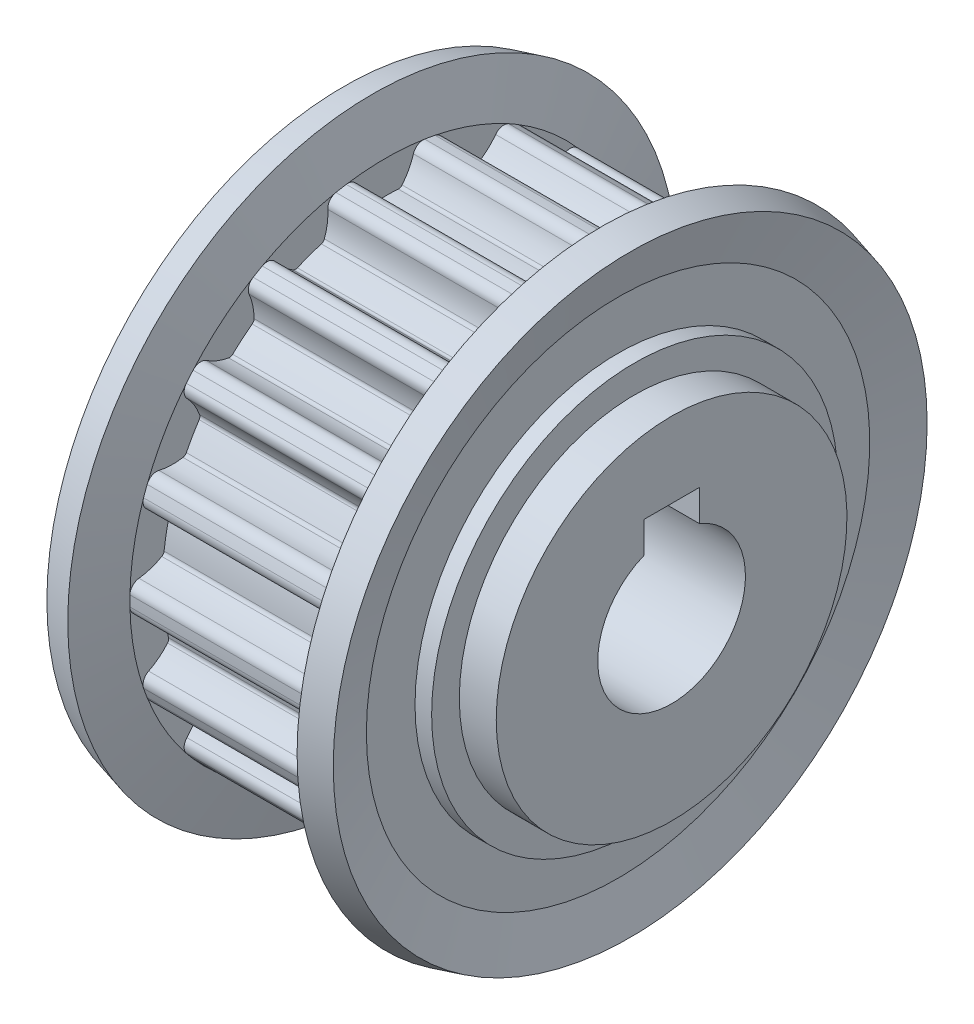
SolidWorks part; units mm, degrees
material "AISI 1045 강, 냉간압연"
ref_plane "정면" through (0, 0, 0) normal (0, 0, 1) x (1, 0, 0)
ref_plane "윗면" through (0, 0, 0) normal (0, 1, 0) x (1, 0, 0)
ref_plane "우측면" through (0, 0, 0) normal (1, 0, 0) x (0, 0, -1)
ref_plane "평면1" through (0, 0, 0) normal (0, 0, 1) x (1, 0, 0)
sketch "스케치1" plane through (0, 0, 0) normal (0, 0, 1) x (1, 0, 0)
  line L0 (0, 0) -> (0, 11)
  line L1 (0, 11) -> (0.9, 11)
  line L2 (0.9, 11) -> (0.9, 13.6344)
  line L3 (0.9, 13.6344) -> (0.2431, 16.0859)
  line L4 (0.2431, 16.0859) -> (1.7886, 16.5)
  line L5 (1.7886, 16.5) -> (2.5, 13.845)
  line L6 (2.5, 13.845) -> (13.5, 13.845)
  line L7 (13.5, 13.845) -> (14.2114, 16.5)
  line L8 (14.2114, 16.5) -> (15.7569, 16.0859)
  line L9 (15.7569, 16.0859) -> (15.1, 13.6344)
  line L10 (15.1, 13.6344) -> (15.1, 11)
  line L11 (15.1, 11) -> (16, 11)
  line L12 (16, 11) -> (16, 9.5)
  line L13 (16, 9.5) -> (25, 9.5)
  line L14 (25, 9.5) -> (25, 0)
  line L15 (25, 0) -> (0, 0)
  line L16 (25, 0) -> (0, 0) construction
revolve "회전1" add sketch "스케치1" angle 360 about L16 reverse direction yes
ref_plane "평면2" through (0, 0, 0) normal (0, 0, 1) x (1, 0, 0)
sketch "스케치2" plane through (0, 0, 0) normal (0, 0, 1) x (1, 0, 0)
  line L0 (0, 0) -> (0, 4)
  line L1 (0, 4) -> (25, 4)
  line L2 (25, 4) -> (25, 0)
  line L3 (25, 0) -> (0, 0)
  line L4 (25, 0) -> (0, 0) construction
revolve "컷-회전1" cut sketch "스케치2" angle 360 about L4 reverse direction yes
ref_plane "평면3" through (2.5, 0, 0) normal (1, 0, 0) x (0, 0, -1)
sketch "스케치3" plane through (2.5, 0, 0) normal (1, 0, 0) x (0, 0, -1)
  line L0 (2.1243, 13.6811) -> (2.1243, 14.1666)
  line L1 (-2.1243, 14.1666) -> (-2.1243, 13.6811)
  arc A0 (-2.1243, 13.6811) -> (-1.5129, 13.295) centre (-2.0399, 13.1376) cw
  arc A1 (-1.5129, 13.295) -> (-0.8988, 12.1454) centre (1.625, 14.2325) ccw
  arc A2 (-0.8988, 12.1454) -> (-0.6918, 12.0552) centre (-0.7062, 12.3048) ccw
  arc A3 (-0.6918, 12.0552) -> (0.6918, 12.0552) centre (0, 0) cw
  arc A4 (0.6918, 12.0552) -> (0.8988, 12.1454) centre (0.7062, 12.3048) ccw
  arc A5 (0.8988, 12.1454) -> (1.5129, 13.295) centre (-1.625, 14.2325) ccw
  arc A6 (1.5129, 13.295) -> (2.1243, 13.6811) centre (2.0399, 13.1376) cw
  arc A7 (2.1243, 14.1666) -> (-2.1243, 14.1666) centre (0, 0) ccw
extrude "컷-돌출1" cut sketch "스케치3" along normal blind 11
ref_plane "평면4" through (2.5, 0, 0) normal (1, 0, 0) x (0, 0, -1)
sketch "스케치4" plane through (2.5, 0, 0) normal (1, 0, 0) x (0, 0, -1)
  line L0 (6.6754, 12.1294) -> (6.8415, 12.5857)
  line L1 (2.8491, 14.0388) -> (2.683, 13.5825)
  arc A0 (2.683, 13.5825) -> (3.1255, 13.0107) centre (2.5764, 13.043) cw
  arc A1 (3.1255, 13.0107) -> (3.3094, 11.7204) centre (6.3948, 12.8184) ccw
  arc A2 (3.3094, 11.7204) -> (3.473, 11.5648) centre (3.5449, 11.8042) ccw
  arc A3 (3.473, 11.5648) -> (4.7732, 11.0915) centre (0, 0) cw
  arc A4 (4.7732, 11.0915) -> (4.9986, 11.1056) centre (4.872, 11.3212) ccw
  arc A5 (4.9986, 11.1056) -> (5.9689, 11.9758) centre (3.3408, 13.93) ccw
  arc A6 (5.9689, 11.9758) -> (6.6754, 12.1294) centre (6.4102, 11.6476) cw
  arc A7 (6.8415, 12.5857) -> (2.8491, 14.0388) centre (0, 0) ccw
extrude "컷-돌출2" cut sketch "스케치4" along normal blind 11
ref_plane "평면5" through (2.5, 0, 0) normal (1, 0, 0) x (0, 0, -1)
sketch "스케치5" plane through (2.5, 0, 0) normal (1, 0, 0) x (0, 0, -1)
  line L0 (10.4213, 9.1148) -> (10.7334, 9.4868)
  line L1 (7.4788, 12.2177) -> (7.1667, 11.8458)
  arc A0 (7.1667, 11.8458) -> (7.3869, 11.1571) centre (6.882, 11.3752) cw
  arc A1 (7.3869, 11.1571) -> (7.1184, 9.8817) centre (10.3933, 9.8582) ccw
  arc A2 (7.1184, 9.8817) -> (7.2189, 9.6795) centre (7.3684, 9.8799) ccw
  arc A3 (7.2189, 9.6795) -> (8.2789, 8.7901) centre (0, 0) cw
  arc A4 (8.2789, 8.7901) -> (8.4955, 8.7262) centre (8.4503, 8.9721) ccw
  arc A5 (8.4955, 8.7262) -> (9.7049, 9.2121) centre (7.9037, 11.9473) ccw
  arc A6 (9.7049, 9.2121) -> (10.4213, 9.1148) centre (10.0073, 8.7527) cw
  arc A7 (10.7334, 9.4868) -> (7.4788, 12.2177) centre (0, 0) ccw
extrude "컷-돌출3" cut sketch "스케치5" along normal blind 11
ref_plane "평면6" through (2.5, 0, 0) normal (1, 0, 0) x (0, 0, -1)
sketch "스케치6" plane through (2.5, 0, 0) normal (1, 0, 0) x (0, 0, -1)
  line L0 (12.9103, 5.0008) -> (13.3308, 5.2436)
  line L1 (11.2065, 8.923) -> (10.786, 8.6802)
  arc A0 (10.786, 8.6802) -> (10.7573, 7.9578) centre (10.3575, 8.3354) cw
  arc A1 (10.7573, 7.9578) -> (10.0688, 6.8511) centre (13.1382, 5.709) ccw
  arc A2 (10.0688, 6.8511) -> (10.0942, 6.6267) centre (10.3032, 6.7639) ccw
  arc A3 (10.0942, 6.6267) -> (10.786, 5.4284) centre (0, 0) cw
  arc A4 (10.786, 5.4284) -> (10.9677, 5.2943) centre (11.0093, 5.5408) ccw
  arc A5 (10.9677, 5.2943) -> (12.2703, 5.3373) centre (11.5132, 8.5236) ccw
  arc A6 (12.2703, 5.3373) -> (12.9103, 5.0008) centre (12.3974, 4.8022) cw
  arc A7 (13.3308, 5.2436) -> (11.2065, 8.923) centre (0, 0) ccw
extrude "컷-돌출4" cut sketch "스케치6" along normal blind 11
ref_plane "평면7" through (2.5, 0, 0) normal (1, 0, 0) x (0, 0, -1)
sketch "스케치7" plane through (2.5, 0, 0) normal (1, 0, 0) x (0, 0, -1)
  line L0 (13.8421, 0.2836) -> (14.3203, 0.368)
  line L1 (13.5825, 4.552) -> (13.1043, 4.4677)
  arc A0 (13.1043, 4.4677) -> (12.8303, 3.7986) centre (12.5838, 4.2902) cw
  arc A1 (12.8303, 3.7986) -> (11.8048, 2.9942) centre (14.2985, 0.8711) ccw
  arc A2 (11.8048, 2.9942) -> (11.7519, 2.7747) centre (11.9952, 2.8321) ccw
  arc A3 (11.7519, 2.7747) -> (11.9922, 1.412) centre (0, 0) cw
  arc A4 (11.9922, 1.412) -> (12.117, 1.2239) centre (12.2404, 1.4413) ccw
  arc A5 (12.117, 1.2239) -> (13.3558, 0.8187) centre (13.7341, 4.0718) ccw
  arc A6 (13.3558, 0.8187) -> (13.8421, 0.2836) centre (13.2922, 0.2724) cw
  arc A7 (14.3203, 0.368) -> (13.5825, 4.552) centre (0, 0) ccw
extrude "컷-돌출5" cut sketch "스케치7" along normal blind 11
ref_plane "평면8" through (2.5, 0, 0) normal (1, 0, 0) x (0, 0, -1)
sketch "스케치8" plane through (2.5, 0, 0) normal (1, 0, 0) x (0, 0, -1)
  line L0 (13.1043, -4.4677) -> (13.5825, -4.552)
  line L1 (14.3203, -0.368) -> (13.8421, -0.2836)
  arc A0 (13.8421, -0.2836) -> (13.3558, -0.8187) centre (13.2922, -0.2724) cw
  arc A1 (13.3558, -0.8187) -> (12.117, -1.2239) centre (13.7341, -4.0718) ccw
  arc A2 (12.117, -1.2239) -> (11.9922, -1.412) centre (12.2404, -1.4413) ccw
  arc A3 (11.9922, -1.412) -> (11.7519, -2.7747) centre (0, 0) cw
  arc A4 (11.7519, -2.7747) -> (11.8048, -2.9942) centre (11.9952, -2.8321) ccw
  arc A5 (11.8048, -2.9942) -> (12.8303, -3.7986) centre (14.2985, -0.8711) ccw
  arc A6 (12.8303, -3.7986) -> (13.1043, -4.4677) centre (12.5838, -4.2902) cw
  arc A7 (13.5825, -4.552) -> (14.3203, -0.368) centre (0, 0) ccw
extrude "컷-돌출6" cut sketch "스케치8" along normal blind 11
ref_plane "평면9" through (2.5, 0, 0) normal (1, 0, 0) x (0, 0, -1)
sketch "스케치9" plane through (2.5, 0, 0) normal (1, 0, 0) x (0, 0, -1)
  line L0 (10.786, -8.6802) -> (11.2065, -8.923)
  line L1 (13.3308, -5.2436) -> (12.9103, -5.0008)
  arc A0 (12.9103, -5.0008) -> (12.2703, -5.3373) centre (12.3974, -4.8022) cw
  arc A1 (12.2703, -5.3373) -> (10.9677, -5.2943) centre (11.5132, -8.5236) ccw
  arc A2 (10.9677, -5.2943) -> (10.786, -5.4284) centre (11.0093, -5.5408) ccw
  arc A3 (10.786, -5.4284) -> (10.0942, -6.6267) centre (0, 0) cw
  arc A4 (10.0942, -6.6267) -> (10.0688, -6.8511) centre (10.3032, -6.7639) ccw
  arc A5 (10.0688, -6.8511) -> (10.7573, -7.9578) centre (13.1382, -5.709) ccw
  arc A6 (10.7573, -7.9578) -> (10.786, -8.6802) centre (10.3575, -8.3354) cw
  arc A7 (11.2065, -8.923) -> (13.3308, -5.2436) centre (0, 0) ccw
extrude "컷-돌출7" cut sketch "스케치9" along normal blind 11
ref_plane "평면10" through (2.5, 0, 0) normal (1, 0, 0) x (0, 0, -1)
sketch "스케치10" plane through (2.5, 0, 0) normal (1, 0, 0) x (0, 0, -1)
  line L0 (7.1667, -11.8458) -> (7.4788, -12.2177)
  line L1 (10.7334, -9.4868) -> (10.4213, -9.1148)
  arc A0 (10.4213, -9.1148) -> (9.7049, -9.2121) centre (10.0073, -8.7527) cw
  arc A1 (9.7049, -9.2121) -> (8.4955, -8.7262) centre (7.9037, -11.9473) ccw
  arc A2 (8.4955, -8.7262) -> (8.2789, -8.7901) centre (8.4503, -8.9721) ccw
  arc A3 (8.2789, -8.7901) -> (7.2189, -9.6795) centre (0, 0) cw
  arc A4 (7.2189, -9.6795) -> (7.1184, -9.8817) centre (7.3684, -9.8799) ccw
  arc A5 (7.1184, -9.8817) -> (7.3869, -11.1571) centre (10.3933, -9.8582) ccw
  arc A6 (7.3869, -11.1571) -> (7.1667, -11.8458) centre (6.882, -11.3752) cw
  arc A7 (7.4788, -12.2177) -> (10.7334, -9.4868) centre (0, 0) ccw
extrude "컷-돌출8" cut sketch "스케치10" along normal blind 11
ref_plane "평면11" through (2.5, 0, 0) normal (1, 0, 0) x (0, 0, -1)
sketch "스케치11" plane through (2.5, 0, 0) normal (1, 0, 0) x (0, 0, -1)
  line L0 (2.683, -13.5825) -> (2.8491, -14.0388)
  line L1 (6.8415, -12.5857) -> (6.6754, -12.1294)
  arc A0 (6.6754, -12.1294) -> (5.9689, -11.9758) centre (6.4102, -11.6476) cw
  arc A1 (5.9689, -11.9758) -> (4.9986, -11.1056) centre (3.3408, -13.93) ccw
  arc A2 (4.9986, -11.1056) -> (4.7732, -11.0915) centre (4.872, -11.3212) ccw
  arc A3 (4.7732, -11.0915) -> (3.473, -11.5648) centre (0, 0) cw
  arc A4 (3.473, -11.5648) -> (3.3094, -11.7204) centre (3.5449, -11.8042) ccw
  arc A5 (3.3094, -11.7204) -> (3.1255, -13.0107) centre (6.3948, -12.8184) ccw
  arc A6 (3.1255, -13.0107) -> (2.683, -13.5825) centre (2.5764, -13.043) cw
  arc A7 (2.8491, -14.0388) -> (6.8415, -12.5857) centre (0, 0) ccw
extrude "컷-돌출9" cut sketch "스케치11" along normal blind 11
ref_plane "평면12" through (2.5, 0, 0) normal (1, 0, 0) x (0, 0, -1)
sketch "스케치12" plane through (2.5, 0, 0) normal (1, 0, 0) x (0, 0, -1)
  line L0 (-2.1243, -13.6811) -> (-2.1243, -14.1666)
  line L1 (2.1243, -14.1666) -> (2.1243, -13.6811)
  arc A0 (2.1243, -13.6811) -> (1.5129, -13.295) centre (2.0399, -13.1376) cw
  arc A1 (1.5129, -13.295) -> (0.8988, -12.1454) centre (-1.625, -14.2325) ccw
  arc A2 (0.8988, -12.1454) -> (0.6918, -12.0552) centre (0.7062, -12.3048) ccw
  arc A3 (0.6918, -12.0552) -> (-0.6918, -12.0552) centre (0, 0) cw
  arc A4 (-0.6918, -12.0552) -> (-0.8988, -12.1454) centre (-0.7062, -12.3048) ccw
  arc A5 (-0.8988, -12.1454) -> (-1.5129, -13.295) centre (1.625, -14.2325) ccw
  arc A6 (-1.5129, -13.295) -> (-2.1243, -13.6811) centre (-2.0399, -13.1376) cw
  arc A7 (-2.1243, -14.1666) -> (2.1243, -14.1666) centre (0, 0) ccw
extrude "컷-돌출10" cut sketch "스케치12" along normal blind 11
ref_plane "평면13" through (2.5, 0, 0) normal (1, 0, 0) x (0, 0, -1)
sketch "스케치13" plane through (2.5, 0, 0) normal (1, 0, 0) x (0, 0, -1)
  line L0 (-6.6754, -12.1294) -> (-6.8415, -12.5857)
  line L1 (-2.8491, -14.0388) -> (-2.683, -13.5825)
  arc A0 (-2.683, -13.5825) -> (-3.1255, -13.0107) centre (-2.5764, -13.043) cw
  arc A1 (-3.1255, -13.0107) -> (-3.3094, -11.7204) centre (-6.3948, -12.8184) ccw
  arc A2 (-3.3094, -11.7204) -> (-3.473, -11.5648) centre (-3.5449, -11.8042) ccw
  arc A3 (-3.473, -11.5648) -> (-4.7732, -11.0915) centre (0, 0) cw
  arc A4 (-4.7732, -11.0915) -> (-4.9986, -11.1056) centre (-4.872, -11.3212) ccw
  arc A5 (-4.9986, -11.1056) -> (-5.9689, -11.9758) centre (-3.3408, -13.93) ccw
  arc A6 (-5.9689, -11.9758) -> (-6.6754, -12.1294) centre (-6.4102, -11.6476) cw
  arc A7 (-6.8415, -12.5857) -> (-2.8491, -14.0388) centre (0, 0) ccw
extrude "컷-돌출11" cut sketch "스케치13" along normal blind 11
ref_plane "평면14" through (2.5, 0, 0) normal (1, 0, 0) x (0, 0, -1)
sketch "스케치14" plane through (2.5, 0, 0) normal (1, 0, 0) x (0, 0, -1)
  line L0 (-10.4213, -9.1148) -> (-10.7334, -9.4868)
  line L1 (-7.4788, -12.2177) -> (-7.1667, -11.8458)
  arc A0 (-7.1667, -11.8458) -> (-7.3869, -11.1571) centre (-6.882, -11.3752) cw
  arc A1 (-7.3869, -11.1571) -> (-7.1184, -9.8817) centre (-10.3933, -9.8582) ccw
  arc A2 (-7.1184, -9.8817) -> (-7.2189, -9.6795) centre (-7.3684, -9.8799) ccw
  arc A3 (-7.2189, -9.6795) -> (-8.2789, -8.7901) centre (0, 0) cw
  arc A4 (-8.2789, -8.7901) -> (-8.4955, -8.7262) centre (-8.4503, -8.9721) ccw
  arc A5 (-8.4955, -8.7262) -> (-9.7049, -9.2121) centre (-7.9037, -11.9473) ccw
  arc A6 (-9.7049, -9.2121) -> (-10.4213, -9.1148) centre (-10.0073, -8.7527) cw
  arc A7 (-10.7334, -9.4868) -> (-7.4788, -12.2177) centre (0, 0) ccw
extrude "컷-돌출12" cut sketch "스케치14" along normal blind 11
ref_plane "평면15" through (2.5, 0, 0) normal (1, 0, 0) x (0, 0, -1)
sketch "스케치15" plane through (2.5, 0, 0) normal (1, 0, 0) x (0, 0, -1)
  line L0 (-12.9103, -5.0008) -> (-13.3308, -5.2436)
  line L1 (-11.2065, -8.923) -> (-10.786, -8.6802)
  arc A0 (-10.786, -8.6802) -> (-10.7573, -7.9578) centre (-10.3575, -8.3354) cw
  arc A1 (-10.7573, -7.9578) -> (-10.0688, -6.8511) centre (-13.1382, -5.709) ccw
  arc A2 (-10.0688, -6.8511) -> (-10.0942, -6.6267) centre (-10.3032, -6.7639) ccw
  arc A3 (-10.0942, -6.6267) -> (-10.786, -5.4284) centre (0, 0) cw
  arc A4 (-10.786, -5.4284) -> (-10.9677, -5.2943) centre (-11.0093, -5.5408) ccw
  arc A5 (-10.9677, -5.2943) -> (-12.2703, -5.3373) centre (-11.5132, -8.5236) ccw
  arc A6 (-12.2703, -5.3373) -> (-12.9103, -5.0008) centre (-12.3974, -4.8022) cw
  arc A7 (-13.3308, -5.2436) -> (-11.2065, -8.923) centre (0, 0) ccw
extrude "컷-돌출13" cut sketch "스케치15" along normal blind 11
ref_plane "평면16" through (2.5, 0, 0) normal (1, 0, 0) x (0, 0, -1)
sketch "스케치16" plane through (2.5, 0, 0) normal (1, 0, 0) x (0, 0, -1)
  line L0 (-13.8421, -0.2836) -> (-14.3203, -0.368)
  line L1 (-13.5825, -4.552) -> (-13.1043, -4.4677)
  arc A0 (-13.1043, -4.4677) -> (-12.8303, -3.7986) centre (-12.5838, -4.2902) cw
  arc A1 (-12.8303, -3.7986) -> (-11.8048, -2.9942) centre (-14.2985, -0.8711) ccw
  arc A2 (-11.8048, -2.9942) -> (-11.7519, -2.7747) centre (-11.9952, -2.8321) ccw
  arc A3 (-11.7519, -2.7747) -> (-11.9922, -1.412) centre (0, 0) cw
  arc A4 (-11.9922, -1.412) -> (-12.117, -1.2239) centre (-12.2404, -1.4413) ccw
  arc A5 (-12.117, -1.2239) -> (-13.3558, -0.8187) centre (-13.7341, -4.0718) ccw
  arc A6 (-13.3558, -0.8187) -> (-13.8421, -0.2836) centre (-13.2922, -0.2724) cw
  arc A7 (-14.3203, -0.368) -> (-13.5825, -4.552) centre (0, 0) ccw
extrude "컷-돌출14" cut sketch "스케치16" along normal blind 11
ref_plane "평면17" through (2.5, 0, 0) normal (1, 0, 0) x (0, 0, -1)
sketch "스케치17" plane through (2.5, 0, 0) normal (1, 0, 0) x (0, 0, -1)
  line L0 (-13.1043, 4.4677) -> (-13.5825, 4.552)
  line L1 (-14.3203, 0.368) -> (-13.8421, 0.2836)
  arc A0 (-13.8421, 0.2836) -> (-13.3558, 0.8187) centre (-13.2922, 0.2724) cw
  arc A1 (-13.3558, 0.8187) -> (-12.117, 1.2239) centre (-13.7341, 4.0718) ccw
  arc A2 (-12.117, 1.2239) -> (-11.9922, 1.412) centre (-12.2404, 1.4413) ccw
  arc A3 (-11.9922, 1.412) -> (-11.7519, 2.7747) centre (0, 0) cw
  arc A4 (-11.7519, 2.7747) -> (-11.8048, 2.9942) centre (-11.9952, 2.8321) ccw
  arc A5 (-11.8048, 2.9942) -> (-12.8303, 3.7986) centre (-14.2985, 0.8711) ccw
  arc A6 (-12.8303, 3.7986) -> (-13.1043, 4.4677) centre (-12.5838, 4.2902) cw
  arc A7 (-13.5825, 4.552) -> (-14.3203, 0.368) centre (0, 0) ccw
extrude "컷-돌출15" cut sketch "스케치17" along normal blind 11
ref_plane "평면18" through (2.5, 0, 0) normal (1, 0, 0) x (0, 0, -1)
sketch "스케치18" plane through (2.5, 0, 0) normal (1, 0, 0) x (0, 0, -1)
  line L0 (-10.786, 8.6802) -> (-11.2065, 8.923)
  line L1 (-13.3308, 5.2436) -> (-12.9103, 5.0008)
  arc A0 (-12.9103, 5.0008) -> (-12.2703, 5.3373) centre (-12.3974, 4.8022) cw
  arc A1 (-12.2703, 5.3373) -> (-10.9677, 5.2943) centre (-11.5132, 8.5236) ccw
  arc A2 (-10.9677, 5.2943) -> (-10.786, 5.4284) centre (-11.0093, 5.5408) ccw
  arc A3 (-10.786, 5.4284) -> (-10.0942, 6.6267) centre (0, 0) cw
  arc A4 (-10.0942, 6.6267) -> (-10.0688, 6.8511) centre (-10.3032, 6.7639) ccw
  arc A5 (-10.0688, 6.8511) -> (-10.7573, 7.9578) centre (-13.1382, 5.709) ccw
  arc A6 (-10.7573, 7.9578) -> (-10.786, 8.6802) centre (-10.3575, 8.3354) cw
  arc A7 (-11.2065, 8.923) -> (-13.3308, 5.2436) centre (0, 0) ccw
extrude "컷-돌출16" cut sketch "스케치18" along normal blind 11
ref_plane "평면19" through (2.5, 0, 0) normal (1, 0, 0) x (0, 0, -1)
sketch "스케치19" plane through (2.5, 0, 0) normal (1, 0, 0) x (0, 0, -1)
  line L0 (-7.1667, 11.8458) -> (-7.4788, 12.2177)
  line L1 (-10.7334, 9.4868) -> (-10.4213, 9.1148)
  arc A0 (-10.4213, 9.1148) -> (-9.7049, 9.2121) centre (-10.0073, 8.7527) cw
  arc A1 (-9.7049, 9.2121) -> (-8.4955, 8.7262) centre (-7.9037, 11.9473) ccw
  arc A2 (-8.4955, 8.7262) -> (-8.2789, 8.7901) centre (-8.4503, 8.9721) ccw
  arc A3 (-8.2789, 8.7901) -> (-7.2189, 9.6795) centre (0, 0) cw
  arc A4 (-7.2189, 9.6795) -> (-7.1184, 9.8817) centre (-7.3684, 9.8799) ccw
  arc A5 (-7.1184, 9.8817) -> (-7.3869, 11.1571) centre (-10.3933, 9.8582) ccw
  arc A6 (-7.3869, 11.1571) -> (-7.1667, 11.8458) centre (-6.882, 11.3752) cw
  arc A7 (-7.4788, 12.2177) -> (-10.7334, 9.4868) centre (0, 0) ccw
extrude "컷-돌출17" cut sketch "스케치19" along normal blind 11
ref_plane "평면20" through (2.5, 0, 0) normal (1, 0, 0) x (0, 0, -1)
sketch "스케치20" plane through (2.5, 0, 0) normal (1, 0, 0) x (0, 0, -1)
  line L0 (-2.683, 13.5825) -> (-2.8491, 14.0388)
  line L1 (-6.8415, 12.5857) -> (-6.6754, 12.1294)
  arc A0 (-6.6754, 12.1294) -> (-5.9689, 11.9758) centre (-6.4102, 11.6476) cw
  arc A1 (-5.9689, 11.9758) -> (-4.9986, 11.1056) centre (-3.3408, 13.93) ccw
  arc A2 (-4.9986, 11.1056) -> (-4.7732, 11.0915) centre (-4.872, 11.3212) ccw
  arc A3 (-4.7732, 11.0915) -> (-3.473, 11.5648) centre (0, 0) cw
  arc A4 (-3.473, 11.5648) -> (-3.3094, 11.7204) centre (-3.5449, 11.8042) ccw
  arc A5 (-3.3094, 11.7204) -> (-3.1255, 13.0107) centre (-6.3948, 12.8184) ccw
  arc A6 (-3.1255, 13.0107) -> (-2.683, 13.5825) centre (-2.5764, 13.043) cw
  arc A7 (-2.8491, 14.0388) -> (-6.8415, 12.5857) centre (0, 0) ccw
extrude "컷-돌출18" cut sketch "스케치20" along normal blind 11
ref_plane "평면21" through (0, 0, 0) normal (1, 0, 0) x (0, 0, -1)
sketch "스케치21" plane through (0, 0, 0) normal (1, 0, 0) x (0, 0, -1)
  line L0 (-1.5, 5.4) -> (-1.5, 0)
  line L1 (-1.5, 0) -> (1.5, 0)
  line L2 (1.5, 0) -> (1.5, 5.4)
  line L3 (1.5, 5.4) -> (-1.5, 5.4)
extrude "컷-돌출19" cut sketch "스케치21" along normal blind 25
ref_plane "평면22" through (20.5, 0, 0) normal (1, 0, 0) x (0, 0, -1)
sketch "스케치22" plane through (20.5, 0, 0) normal (1, 0, 0) x (0, 0, -1)
  line L0 (0, 9.5) -> (1.621, 9.5)
  line L1 (1.621, 9.5) -> (1.621, 0)
  line L2 (1.621, 0) -> (0, 0)
  line L3 (0, 0) -> (0, 9.5)
  line L4 (0, 0) -> (0, 9.5) construction
revolve "컷-회전2" cut sketch "스케치22" angle 360 about L4 reverse direction yes
ref_plane "평면23" through (20.5, 0, 0) normal (1, 0, 0) x (0, 0, -1)
sketch "스케치23" plane through (20.5, 0, 0) normal (1, 0, 0) x (0, 0, -1)
  line L0 (8.2272, -4.75) -> (7.4167, -6.1538)
  line L1 (7.4167, -6.1538) -> (-0.8105, -1.4038)
  line L2 (-0.8105, -1.4038) -> (0, 0)
  line L3 (0, 0) -> (8.2272, -4.75)
  line L4 (0, 0) -> (8.2272, -4.75) construction
revolve "컷-회전3" cut sketch "스케치23" angle 360 about L4 reverse direction yes
sketch "스케치24" plane through (0, 0, 0) normal (0, 0, 1) x (1, 0, 0)
  line L0 (0, 11) -> (0, -11) construction
  line L1 (25, 9.5) -> (18, 9.5)
  line L2 (25, 9.5) -> (25, 0)
  line L3 (25, 0) -> (18, 0)
  line L4 (18, 9.5) -> (18, 0)
  dimension "D1" = 18
revolve "컷-회전4" cut sketch "스케치24" angle 360 about L3
